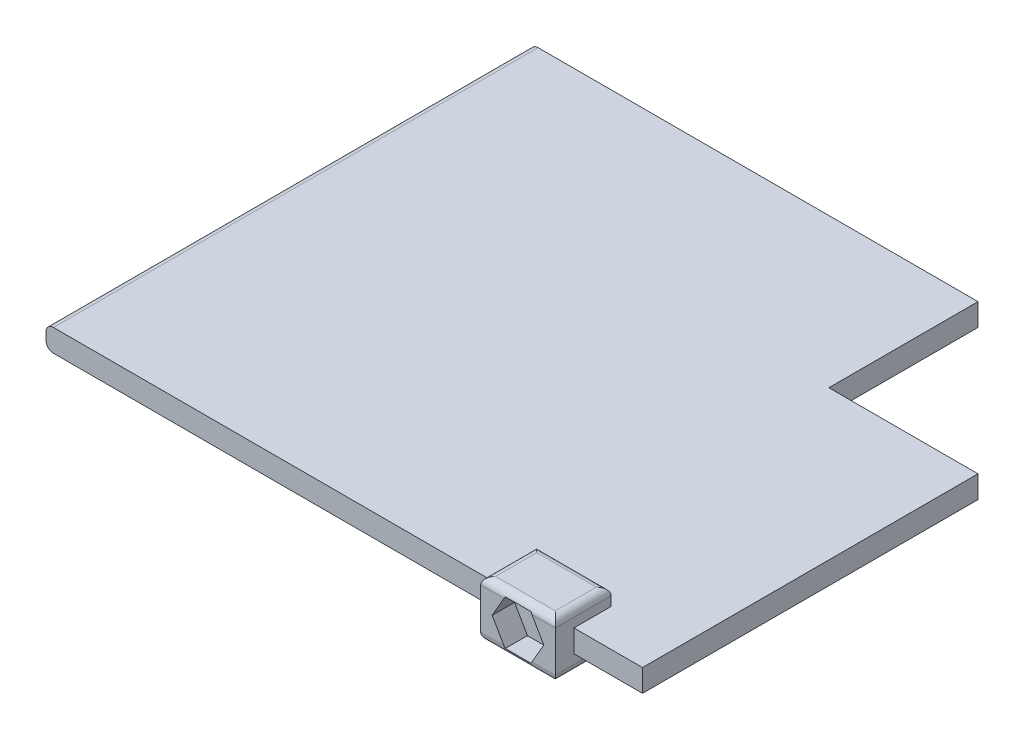
SolidWorks part; units mm, degrees
ref_plane "Front Plane" through (0, 0, 0) normal (0, 0, 1) x (1, 0, 0)
ref_plane "Top Plane" through (0, 0, 0) normal (0, 1, 0) x (1, 0, 0)
ref_plane "Right Plane" through (0, 0, 0) normal (1, 0, 0) x (0, 0, -1)
other "Center of Mass"
sketch "Sketch2" plane through (0, 0, 0) normal (0, 1, 0) x (1, 0, 0)
  line L1 (-80, -65) -> (80, -65)
  line L2 (-80, -65) -> (-80, 65)
  line L3 (-80, 65) -> (80, 65)
  line L4 (80, -65) -> (80, 65)
  line L5 (-80, -65) -> (80, 65) construction
  line L6 (-80, 65) -> (80, -65) construction
  point P0 (0, 0)
  dimension "D1" = 160
  dimension "D2" = 130
extrude "Boss-Extrude1" add sketch "Sketch2" along normal blind 6
sketch "Sketch7" plane through (0, 6, 0) normal (0, 1, 0) x (1, 0, 0)
  line L1 (80, 65) -> (40, 65)
  line L2 (80, 65) -> (80, 25)
  line L3 (80, 25) -> (40, 25)
  line L4 (40, 65) -> (40, 25)
  line L5 (80, 65) -> (40, 25) construction
  line L6 (80, 25) -> (40, 65) construction
  point P4 (60, 45)
  dimension "D1" = 40
  dimension "D2" = 40
extrude "Cut-Extrude1" cut sketch "Sketch7" against normal blind 18
sketch "Sketch9" plane through (0, 0, 65) normal (0, 0, 1) x (1, 0, 0)
  circle A0 centre (51.6061, 2.9782) radius 2
  dimension "D1" = 4
extrude "Cut-Extrude2" cut sketch "Sketch9" against normal blind 63
sketch "Sketch11" plane through (0, 0, 65) normal (0, 0, 1) x (1, 0, 0)
  line L1 (41.6061, -4.5218) -> (61.6061, -4.5218)
  line L2 (41.6061, -4.5218) -> (41.6061, 10.4782)
  line L3 (41.6061, 10.4782) -> (61.6061, 10.4782)
  line L4 (61.6061, -4.5218) -> (61.6061, 10.4782)
  line L5 (41.6061, -4.5218) -> (61.6061, 10.4782) construction
  line L6 (41.6061, 10.4782) -> (61.6061, -4.5218) construction
  point P0 (51.6061, 2.9782)
  dimension "D1" = 20
  dimension "D2" = 15
extrude "Boss-Extrude2" add sketch "Sketch11" against normal blind 10 and the other way blind 5
sketch "Sketch12" plane through (0, 0, 70) normal (0, 0, 1) x (1, 0, 0)
  line L0 (51.6061, 10.4782) -> (51.6061, -4.5218) construction
  line L1 (61.6061, 10.4782) -> (41.6061, 10.4782) construction
  line L2 (41.6061, -4.5218) -> (61.6061, -4.5218) construction
  line L3 (41.6061, 2.9782) -> (61.6061, 2.9782) construction
  line L4 (61.6061, -4.5218) -> (61.6061, 10.4782) construction
  line L6 (55.0728, -3.0203) -> (58.5343, 2.9813)
  line L7 (58.5343, 2.9813) -> (55.0675, 8.9797)
  line L8 (55.0675, 8.9797) -> (48.1393, 8.9767)
  line L9 (48.1393, 8.9767) -> (44.6779, 2.9752)
  line L10 (44.6779, 2.9752) -> (48.1446, -3.0233)
  line L11 (48.1446, -3.0233) -> (55.0728, -3.0203)
  circle A0 centre (51.6061, 2.9782) radius 6 construction
  point P11 (51.6061, 2.9782)
  dimension "D1" = 12
extrude "Cut-Extrude4" cut sketch "Sketch12" against normal blind 6
sketch "Sketch13" plane through (0, 0, 64) normal (0, 0, 1) x (1, 0, 0)
  line L0 (51.6061, 10.4782) -> (51.6061, -4.5218) construction
  line L1 (61.6061, 10.4782) -> (41.6061, 10.4782) construction
  line L2 (41.6061, -4.5218) -> (61.6061, -4.5218) construction
  line L3 (41.6061, 2.9782) -> (61.6061, 2.9782) construction
  line L4 (61.6061, -4.5218) -> (61.6061, 10.4782) construction
  circle A0 centre (51.6061, 2.9782) radius 2
  point P11 (51.6061, 2.9782)
extrude "Cut-Extrude5" cut sketch "Sketch13" against normal blind 222
fillet "Fillet4" radius 2 2 edges at (-80, 6, 0) (-80, 0, 0)
fillet "Fillet5" radius 2 4 edges at (51.6061, -4.5218, 70) (61.6061, -4.5218, 62.5) (51.6061, -4.5218, 55) (41.6061, -4.5218, 62.5)
fillet "Fillet6" radius 2 4 edges at (51.6061, 10.4782, 70) (41.6061, 10.4782, 62.5) (51.6061, 10.4782, 55) (61.6061, 10.4782, 62.5)
